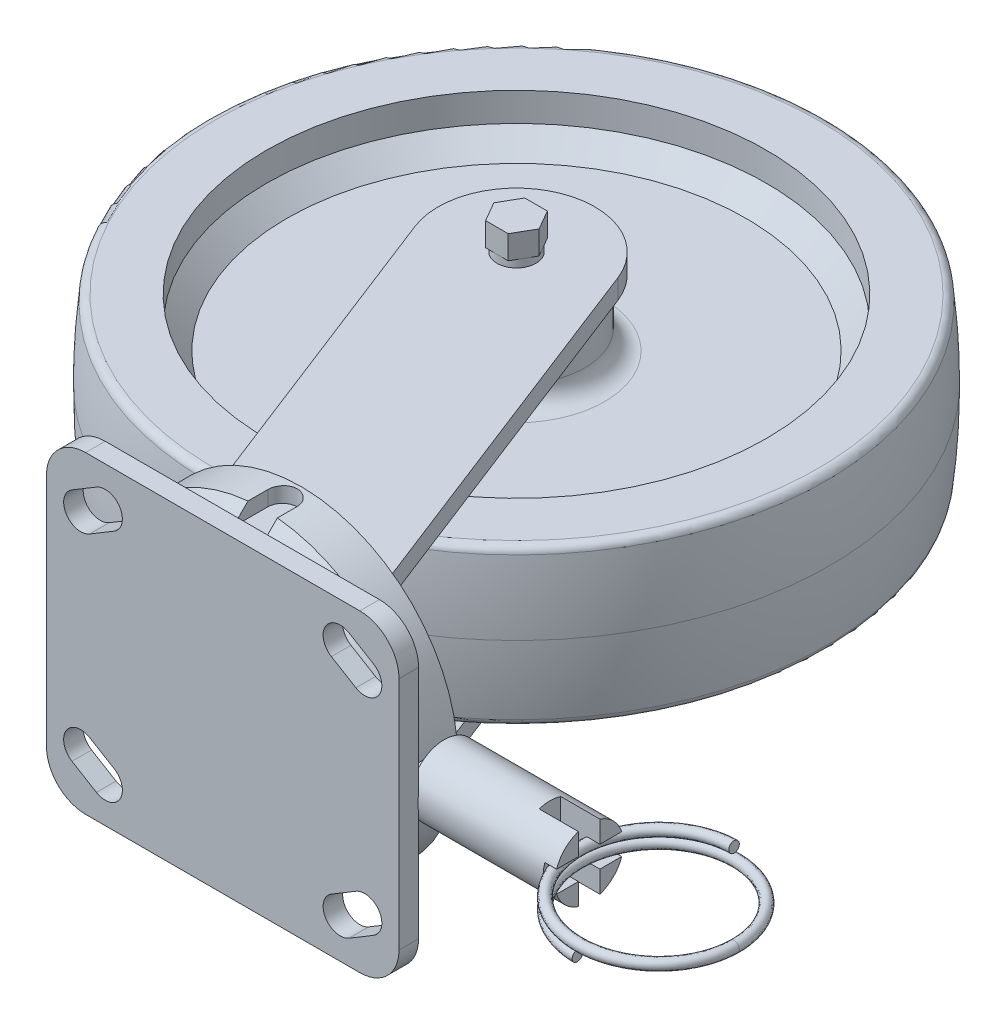
SolidWorks part; units mm, degrees
ref_plane "Front" through (0, 0, 0) normal (0, 0, 1) x (1, 0, 0)
ref_plane "Top" through (0, 0, 0) normal (0, 1, 0) x (1, 0, 0)
ref_plane "Right" through (0, 0, 0) normal (1, 0, 0) x (0, 0, -1)
sketch "Sketch1" plane through (0, 0, 0) normal (0, 0, 1) x (1, 0, 0)
  line L0 (0, 22.225) -> (0, 0) construction
  line L1 (-22.225, 0) -> (0, 0) construction
  line L2 (0, 0) -> (0, -30.1625)
  line L3 (0, -30.1625) -> (22.225, -30.1625)
  line L4 (22.225, -30.1625) -> (22.225, -15.875)
  line L5 (28.575, -9.525) -> (74.4504, -9.525)
  line L6 (81.026, -16.1006) -> (81.026, -25.4)
  line L7 (81.026, -25.4) -> (100.076, -25.4)
  line L8 (44.45, 0) -> (44.45, -9.525) construction
  line L9 (101.6, 0) -> (0, 0)
  line L10 (44.45, -9.525) -> (44.45, -30.9245) construction
  line L11 (84.7528, -30.9245) -> (4.1472, -30.9245) construction
  line L12 (0, -30.9245) -> (0, -30.1625) construction
  line L13 (4.1472, -30.9245) -> (0, -30.9245) construction
  line L14 (9.9355, -37.2745) -> (78.9645, -37.2745) construction
  line L15 (74.4504, -9.525) -> (81.026, -16.1006)
  arc A0 (101.6, 0) -> (100.076, -25.4) centre (-110.8287, 0) cw
  circle A1 centre (44.45, 0) radius 50.8 construction
  arc A2 (28.575, -9.525) -> (22.225, -15.875) centre (28.575, -15.875) ccw
  dimension "Plate Width" = 101.6
  dimension "D7" = 6.35
  dimension "Wheel Dia" = 203.2
  dimension "Wheel Width" = 50.8
  dimension "D4" = 60.325
  dimension "D6" = 44.45
  dimension "Swivel Lead" = 44.45
  dimension "D1" = 0.762
  dimension "Leg Thickness" = 6.35
  dimension "D2" = 9.525
  dimension "D3" = 1.524
  dimension "Wheel Thickness" = 19.05
  dimension "D8" = 135
revolve "Revolve1" add sketch "Sketch1" angle 360 about L0
fillet "Fillet4" radius 2.54 1 edges at (-100.076, -25.4, 0)
chamfer "Chamfer1" distance 1.524 angle 45 1 edges at (-22.225, -30.1625, 0)
ref_plane "Plane1" through (0, -30.9245, 0) normal (0, -1, 0) x (1, 0, 0)
sketch "Sketch3" plane through (0, -30.9245, 0) normal (0, -1, 0) x (1, 0, 0)
  line L0 (-23.6729, 9.2061) -> (17.1969, 114.3)
  line L1 (17.1969, 120.65) -> (71.7031, 120.65) construction
  line L2 (71.7031, 114.3) -> (23.6729, -9.2061)
  line L3 (44.45, 120.65) -> (44.45, 133.35) construction
  line L4 (71.7031, 114.3) -> (17.1969, 114.3)
  line L5 (71.7031, 114.3) -> (71.7031, 120.65) construction
  line L6 (17.1969, 120.65) -> (17.1969, 114.3) construction
  line L7 (44.45, 0) -> (44.45, 120.65) construction
  line L8 (-12.7, 139.7) -> (101.6, 139.7) construction
  line L9 (-12.7, 139.7) -> (-12.7, 133.35) construction
  line L10 (-12.7, 133.35) -> (101.6, 133.35) construction
  line L11 (101.6, 139.7) -> (101.6, 133.35) construction
  line L14 (0, 0) -> (44.45, 114.3) construction
  arc A0 (-23.6729, 9.2061) -> (23.6729, -9.2061) centre (0, 0) ccw
  circle A2 centre (0, 0) radius 101.6 construction
  point P11 (44.45, 120.65)
  point P18 (44.45, 133.35)
  dimension "D1" = 50.8
  dimension "D3" = 12.7
  dimension "Overall Height" = 241.3
  dimension "Plate Thickness" = 6.35
  dimension "Plate Length" = 114.3
extrude "Extrude1" add sketch "Sketch3" along normal blind 6.35 separate body
sketch "Sketch7" plane through (0, 0, 0) normal (0, 1, 0) x (1, 0, 0)
  line L1 (-12.7, -139.7) -> (101.6, -139.7)
  line L2 (-12.7, -139.7) -> (-12.7, -133.35)
  line L3 (-12.7, -133.35) -> (101.6, -133.35)
  line L4 (101.6, -139.7) -> (101.6, -133.35)
extrude "Extrude2" add sketch "Sketch7" against normal blind 50.8 separate body
sketch "Sketch20" plane through (0, 0, 114.3) normal (0, 0, 1) x (1, 0, 0)
  line L0 (-6.35, 0) -> (95.25, 0)
  arc A1 (-6.35, 0) -> (95.25, 0) centre (44.45, 0) ccw
  circle A2 centre (44.45, 0) radius 50.8 construction
extrude "Extrude8" add sketch "Sketch20" along normal up to vertex (6.35 mm away) up to point (44.45, -30.9245, 120.65)
sketch "Sketch24" plane through (0, 0, 114.3) normal (0, 0, -1) x (-1, 0, 0)
  line L0 (-69.85, 0) -> (-19.05, 0)
  line L1 (6.35, 0) -> (-95.25, 0) construction
  arc A0 (-69.85, 0) -> (-19.05, 0) centre (-44.45, 0) ccw
  dimension "D1" = 50.8
extrude "Extrude10" add sketch "Sketch24" along normal blind 3.175
sketch "Sketch8" plane through (0, 0, 120.65) normal (0, 0, 1) x (1, 0, 0)
  line L0 (-6.35, 0) -> (12.7, 0)
  line L1 (76.2, 0) -> (95.25, 0)
  arc A0 (12.7, 0) -> (76.2, 0) centre (44.45, 0) ccw
  arc A1 (-6.35, 0) -> (95.25, 0) centre (44.45, 0) ccw
  circle A4 centre (44.45, 0) radius 50.8 construction
  dimension "D1" = 19.05
extrude "Extrude3" add sketch "Sketch8" along normal offset from surface (11.176 mm away) 1.524 up to face at (44.45, -25.4, 133.35)
chamfer "Chamfer2" distance 5.08 angle 45 1 edges at (44.45, -50.8, 131.826)
sketch "Sketch9" plane through (0, 0, 133.35) normal (0, 0, -1) x (-1, 0, 0)
  line L0 (6.35, 0) -> (-12.7, 0) construction
  line L1 (-44.45, -31.75) -> (-44.45, -25.4) construction
  line L3 (-69.85, 0) -> (-50.8, 0)
  line L4 (-38.1, 0) -> (-19.05, 0)
  arc A0 (-69.85, 0) -> (-19.05, 0) centre (-44.45, 0) ccw
  arc A1 (-50.8, 0) -> (-38.1, 0) centre (-44.45, 0) ccw
  arc A3 (-76.2, 0) -> (-12.7, 0) centre (-44.45, 0) ccw construction
  arc A4 (-76.2, 0) -> (-12.7, 0) centre (-44.45, 0) ccw construction
  dimension "D1" = 6.35
extrude "Extrude4" add sketch "Sketch9" along normal offset from surface (11.43 mm away) 1.27 up to face at (76.2, 0, 120.65)
chamfer "Chamfer3" distance 5.08 angle 45 1 edges
sketch "Sketch10" plane through (0, 0, 139.7) normal (0, 0, 1) x (1, 0, 0)
  line L0 (44.45, 0) -> (44.45, -50.8) construction
  line L1 (1.2712, -28.5731) -> (9.2087, -33.3356)
  line L2 (101.6, -50.8) -> (-12.7, -50.8) construction
  line L3 (-4.4462, -38.1019) -> (3.4913, -42.8644)
  line L4 (85.4087, -42.8644) -> (93.3462, -38.1019)
  line L5 (0, 0) -> (44.45, 0) construction
  line L6 (101.6, 0) -> (-101.6, 0) construction
  line L7 (87.6288, -28.5731) -> (79.6913, -33.3356)
  arc A0 (3.4913, -42.8644) -> (9.2087, -33.3356) centre (6.35, -38.1) ccw
  arc A1 (1.2712, -28.5731) -> (-4.4462, -38.1019) centre (-1.5875, -33.3375) ccw
  arc A2 (87.6288, -28.5731) -> (93.3462, -38.1019) centre (90.4875, -33.3375) cw
  arc A3 (79.6913, -33.3356) -> (85.4087, -42.8644) centre (82.55, -38.1) ccw
  dimension "D1" = 5.5562
  dimension "D2" = 76.2
  dimension "D3" = 76.2
  dimension "Hole1 Width" = 66.675
  dimension "Hole1 Length" = 92.075
extrude "Cut-Extrude1" cut sketch "Sketch10" against normal up to next (6.35 mm away)
fillet "Fillet1" radius 12.7 2 edges at (101.6, -50.8, 136.525) (-12.7, -50.8, 136.525)
sketch "Sketch11" plane through (0, -30.9245, 0) normal (0, 1, 0) x (-1, 0, 0)
  line L0 (0, 55.88) -> (0, -55.88) construction
  line L1 (55.88, 0) -> (-55.88, 0) construction
  circle A0 centre (0, 0) radius 6.35
  dimension "Bolt Size" = 12.7
extrude "Cut-Extrude2" cut sketch "Sketch11" against normal through all and the other way through all
sketch "Sketch12" plane through (0, 0, 0) normal (0, 1, 0) x (-1, 0, 0)
  line L0 (0, 6.3246) -> (0, 6.35) construction
  circle A0 centre (0, 0) radius 6.3246
  circle A2 centre (0, 0) radius 6.35 construction
  circle A3 centre (0, 0) radius 6.35 construction
  dimension "D1" = 0.0254
extrude "Extrude5" add sketch "Sketch12" against normal offset from surface (39.8145 mm away) 2.54 separate body up to face at (6.35, -37.2745, 0) offset beyond the face yes
sketch "Sketch13" plane through (0, -39.8145, 0) normal (0, -1, 0) x (1, 0, 0)
  line L1 (3.6662, 6.35) -> (-3.6662, 6.35)
  line L2 (-3.6662, 6.35) -> (-7.3323, 0)
  line L3 (-7.3323, 0) -> (-3.6662, -6.35)
  line L4 (-3.6662, -6.35) -> (3.6662, -6.35)
  line L5 (3.6662, -6.35) -> (7.3323, 0)
  line L6 (7.3323, 0) -> (3.6662, 6.35)
  circle A0 centre (0, 0) radius 6.35 construction
  circle A1 centre (0, 0) radius 6.35 construction
  circle A2 centre (0, 0) radius 6.3246 construction
extrude "Extrude6" add sketch "Sketch13" along normal blind 7.62
mirror "Mirror1" about plane through (0, 0, 0) normal (0, 1, 0) of bodies 115 116 117 119 108
split line "Split Line1"
ref_plane "Plane2" through (95.25, 0, 0) normal (1, 0, 0) x (0, 0, -1)
sketch "Sketch32" plane through (95.25, 0, 0) normal (1, 0, 0) x (0, 0, -1)
  line L0 (-131.826, 4.7625) -> (-120.3325, 4.7625)
  line L1 (-120.3325, -4.7625) -> (-131.826, -4.7625)
  line L2 (-131.826, -4.7625) -> (-131.826, 4.7625)
  line L3 (-131.826, 45.72) -> (-131.826, -45.72) construction
  line L4 (-114.3, 0) -> (-120.3325, 0) construction
  arc A0 (-120.3325, 4.7625) -> (-120.3325, -4.7625) centre (-120.3325, 0) cw
  dimension "D1" = 9.525
  dimension "D2" = 1.27
extrude "Cut-Extrude7" cut sketch "Sketch32" against normal blind 5.08
pattern_circular "CirPattern3" count 4 over 360 about axis through (44.45, 0, 0) along (0, 0, 1) of "Cut-Extrude7"
sketch "Sketch33" plane through (0, 0, 0) normal (0, 1, 0) x (1, 0, 0)
  line L0 (92.71, -117.7925) -> (99.06, -117.7925)
  line L1 (99.06, -117.7925) -> (99.06, -111.379)
  line L2 (99.06, -111.379) -> (146.05, -111.379)
  line L3 (146.05, -111.379) -> (146.05, -122.4915)
  line L4 (146.05, -133.604) -> (99.06, -133.604) construction
  line L5 (99.06, -133.604) -> (99.06, -127.1905) construction
  line L6 (99.06, -127.1905) -> (92.71, -127.1905) construction
  line L7 (92.71, -127.1905) -> (92.71, -122.4915) construction
  line L8 (88.9, -133.35) -> (0, -133.35) construction
  line L9 (95.25, -131.826) -> (95.25, -120.3325) construction
  line L10 (92.71, -122.4915) -> (146.05, -122.4915)
  line L11 (92.71, -122.4915) -> (92.71, -117.7925)
  line L12 (146.05, -122.4915) -> (146.05, -133.604) construction
  line L13 (101.6, -139.7) -> (101.6, -133.35) construction
  dimension "D1" = 9.398
  dimension "D2" = 0.254
  dimension "D3" = 2.54
  dimension "D4" = 6.35
  dimension "D5" = 22.225
  dimension "D6" = 44.45
revolve "Revolve2" add sketch "Sketch33" angle 360 about L10
sketch "Sketch34" plane through (146.05, 0, 0) normal (1, 0, 0) x (0, 0, -1)
  line L0 (-125.984, -11.1125) -> (-118.999, 11.1125) construction
  line L1 (-125.984, -11.1125) -> (-118.999, -11.1125)
  line L2 (-125.984, -11.1125) -> (-125.984, 11.1125)
  line L3 (-125.984, 11.1125) -> (-118.999, 11.1125)
  line L4 (-118.999, -11.1125) -> (-118.999, 11.1125)
  circle A1 centre (-122.4915, 0) radius 11.1125 construction
  circle A2 centre (-122.4915, 0) radius 11.1125 construction
  dimension "D1" = 6.985
extrude "Cut-Extrude8" cut sketch "Sketch34" against normal blind 12.7
sketch "Sketch35" plane through (146.05, 0, 0) normal (1, 0, 0) x (0, 0, -1)
  line L0 (-125.984, 11.1125) -> (-118.999, 11.1125) construction
  line L1 (-133.604, -3.4925) -> (-111.379, -3.4925)
  line L2 (-133.604, -3.4925) -> (-133.604, 3.4925)
  line L3 (-133.604, 3.4925) -> (-111.379, 3.4925)
  line L4 (-111.379, -3.4925) -> (-111.379, 3.4925)
  line L5 (-111.379, -3.4925) -> (-133.604, 3.4925) construction
  line L6 (-125.984, -11.1125) -> (-125.984, 11.1125) construction
extrude "Cut-Extrude9" cut sketch "Sketch35" against normal blind 3.81
sketch "Sketch37" plane through (0, 0, 0) normal (0, 1, 0) x (1, 0, 0)
  line L0 (142.24, -125.984) -> (142.24, -133.0409) construction
  line L1 (146.05, -122.4915) -> (167.64, -122.4915) construction
  circle A0 centre (167.64, -122.4915) radius 25.4
  dimension "D1" = 50.8
curve "Helix/Spiral1" pitch 3.4544 height 2.5908 turns 0.75
ref_plane "Plane3" through (193.04, 0, 122.4915) normal (0, 0.0216, 0.9998) x (1, 0, 0)
sketch "Sketch38" plane through (193.04, 0, 122.4915) normal (0, 0.0216, 0.9998) x (1, 0, 0)
  circle A0 centre (0, 0) radius 1.7145
  dimension "D1" = 3.429
sweep "Sweep1" add profiles "Sketch38" path "Helix/Spiral1"
sketch "Sketch39" plane through (0, 0, 0) normal (0, 1, 0) x (1, 0, 0)
  circle A0 centre (167.64, -122.4915) radius 25.4 construction
  circle A1 centre (167.64, -122.4915) radius 25.4
curve "Helix/Spiral2" pitch 3.4544 height 2.5908 turns 0.75
sketch "Sketch40" plane through (193.04, 0, 122.4915) normal (0, 0.0216, 0.9998) x (1, 0, 0)
  circle A0 centre (0, 0) radius 1.7145 construction
  circle A1 centre (0, 0) radius 1.7145
sweep "Sweep2" add profiles "Sketch40" path "Helix/Spiral2"
equation "\"D4@Sketch1\"=\"Wheel Width@Sketch1\"+.375"
equation "\"Plate Width@Extrude2\"=\"Plate Width@Sketch1\"/2"
equation "\"D2@Extrude1\"=\"Leg Thickness@Sketch1\""
